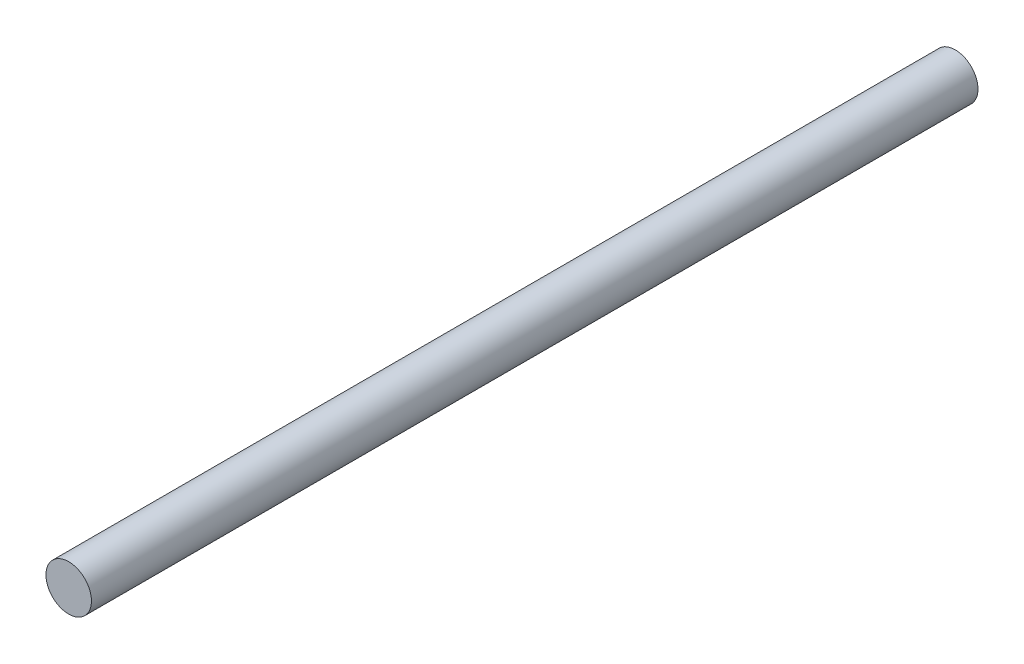
SolidWorks part; units mm, degrees
ref_plane "Front Plane" through (0, 0, 0) normal (0, 0, 1) x (1, 0, 0)
ref_plane "Top Plane" through (0, 0, 0) normal (0, 1, 0) x (1, 0, 0)
ref_plane "Right Plane" through (0, 0, 0) normal (1, 0, 0) x (0, 0, -1)
sketch "Sketch1" plane through (0, 0, 0) normal (0, 0, 1) x (1, 0, 0)
  circle A0 centre (0, 0) radius 5
  dimension "D1" = 10
extrude "Boss-Extrude1" add sketch "Sketch1" along normal blind 195
